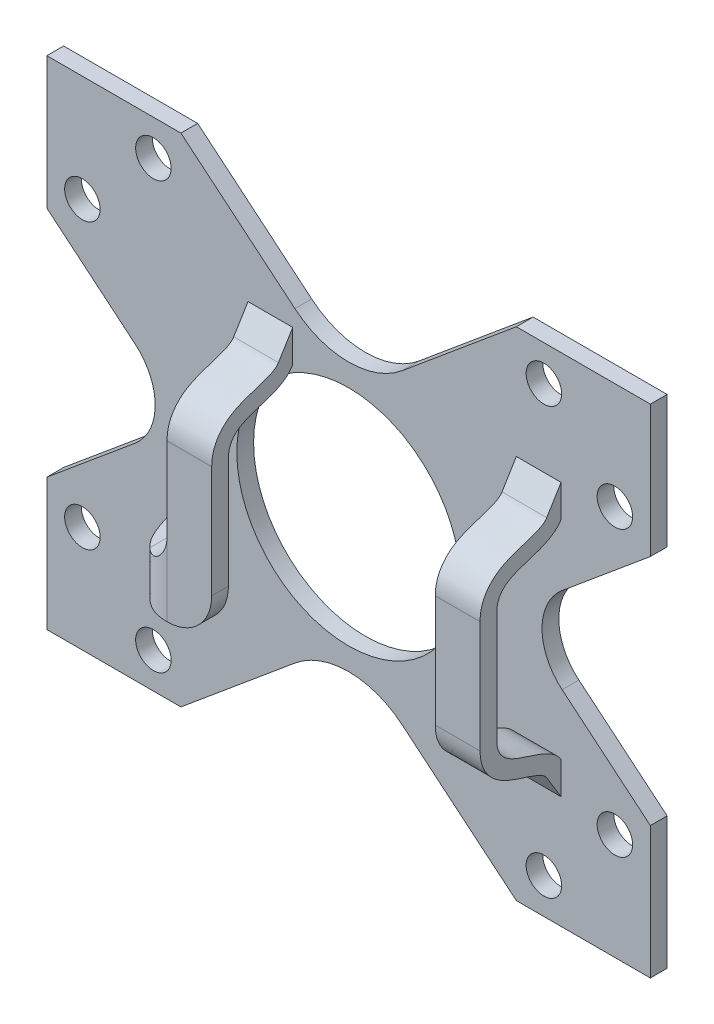
SolidWorks part; units mm, degrees
ref_plane "Front Plane" through (0, 0, 0) normal (0, 0, 1) x (1, 0, 0)
ref_plane "Top Plane" through (0, 0, 0) normal (0, 1, 0) x (1, 0, 0)
ref_plane "Right Plane" through (0, 0, 0) normal (1, 0, 0) x (0, 0, -1)
sketch "Sketch1" plane through (0, 0, 0) normal (0, 0, 1) x (1, 0, 0)
  line L1 (-53.975, -44.45) -> (53.975, -44.45)
  line L2 (-53.975, -44.45) -> (-53.975, 44.45)
  line L3 (-53.975, 44.45) -> (53.975, 44.45)
  line L4 (53.975, -44.45) -> (53.975, 44.45)
  line L5 (-53.975, -44.45) -> (53.975, 44.45) construction
  line L6 (-53.975, 44.45) -> (53.975, -44.45) construction
  line L12 (0, 44.45) -> (0, 19.45) construction
  line L13 (9.6028, 27.4523) -> (30, 44.45)
  line L14 (-9.6028, 27.4523) -> (-30, 44.45)
  line L15 (-9.6028, -27.4523) -> (-30, -44.45)
  line L16 (9.6028, -27.4523) -> (30, -44.45)
  line L17 (53.975, 0) -> (28.975, 0) construction
  line L18 (38.1937, 7.6822) -> (53.975, 20.8333)
  line L19 (38.1937, -7.6822) -> (53.975, -20.8333)
  line L20 (-38.1937, -7.6822) -> (-53.975, -20.8333)
  line L21 (-38.1937, 7.6822) -> (-53.975, 20.8333)
  circle A0 centre (34.925, 38.1) radius 3.175
  circle A1 centre (-34.925, 38.1) radius 3.175
  circle A2 centre (-47.625, 25.4) radius 3.175
  circle A3 centre (-47.625, -25.4) radius 3.175
  circle A4 centre (-34.925, -38.1) radius 3.175
  circle A5 centre (34.925, -38.1) radius 3.175
  circle A6 centre (47.625, -25.4) radius 3.175
  circle A7 centre (47.625, 25.4) radius 3.175
  circle A8 centre (0, 0) radius 20
  arc A9 (9.6028, -27.4523) -> (-9.6028, -27.4523) centre (0, -38.9756) ccw
  arc A10 (-9.6028, 27.4523) -> (9.6028, 27.4523) centre (0, 38.9756) ccw
  arc A11 (-38.1937, 7.6822) -> (-38.1937, -7.6822) centre (-44.5955, 0) cw
  arc A12 (38.1937, 7.6822) -> (38.1937, -7.6822) centre (44.5955, 0) ccw
  point P0 (0, 0)
  point P45 (0, 0)
  point P54 (0, 0)
  dimension "D3" = 40
  dimension "D8" = 15
  dimension "D9" = 10
  dimension "D4" = 25
  dimension "D5" = 30
  dimension "D7" = 2
  dimension "D6" = 2
extrude "Boss-Extrude1" add sketch "Sketch1" along normal blind 3 contours A12 L18 L4 L3 L13 A10 L14 L2 L21 A11 L20 L1 L15 A9 L16 L19 A8 A7 A6 A5 A4 A3 A2 A1 A0 region at (-52.5766, -32.6417, 0)
sketch "Sketch2" plane through (30, 0, 0) normal (1, 0, 0) x (0, 1, 0)
  line L0 (10, 44.6) -> (10, 14) construction
  line L1 (10, 14.5) -> (-10, 14.5)
  line L2 (10, 14.5) -> (10, 17.5)
  line L3 (10, 17.5) -> (-10, 17.5)
  line L4 (-10, 14.5) -> (-10, 17.5)
  line L5 (-10, 44.6) -> (-10, 14) construction
  line L6 (-27.4523, 3) -> (-44.45, 3) construction
  line L7 (0, 17.5) -> (0, 14.5) construction
  line L8 (18.5899, 3) -> (24.3467, 3)
  line L9 (20.1533, 5.5604) -> (24.3467, 3)
  line L10 (20.8333, 3) -> (44.45, 3) construction
  line L11 (-20.1533, 5.5604) -> (-24.3467, 3)
  line L12 (-18.5899, 3) -> (-24.3467, 3)
  line L13 (10, 14.5) -> (10, 17.5)
  line L16 (10.0308, 17.4998) -> (10, 17.5)
  line L17 (-10, 17.5) -> (-10.0308, 17.4998)
  spline S0 degree 3 poles (10, 14.5) (16.0446, 14.4379) (14.1847, 5.6897) (18.5899, 3) knots 0 0 0 0 1 1 1 1
  spline S1 degree 1 poles (10.0308, 17.4998) (20.1533, 5.5604) knots 0 0 1 1 construction
  spline S2 degree 3 poles (10.0308, 17.4998) (10.5803, 17.4942) (11.6908, 17.3812) (13.7449, 16.6992) (15.7401, 15.0501) (17.0126, 12.7979) (17.7868, 10.6515) (18.3801, 8.6858) (18.9697, 7.0604) (19.4886, 6.1722) (19.8692, 5.7606) (20.0511, 5.6229) (20.1533, 5.5604) knots 0 0 0 0 0.0625 0.125 0.25 0.375 0.5 0.625 0.75 0.875 0.9375 1 1 1 1
  spline S3 degree 3 poles (-10, 14.5) (-16.0446, 14.4379) (-14.1847, 5.6897) (-18.5899, 3) knots 0 0 0 0 1 1 1 1
  spline S4 degree 3 poles (-10.0308, 17.4998) (-10.5803, 17.4942) (-11.6908, 17.3812) (-13.7449, 16.6992) (-15.7401, 15.0501) (-17.0126, 12.7979) (-17.7868, 10.6515) (-18.3801, 8.6858) (-18.9697, 7.0604) (-19.4886, 6.1722) (-19.8692, 5.7606) (-20.0511, 5.6229) (-20.1533, 5.5604) knots 0 0 0 0 0.0625 0.125 0.25 0.375 0.5 0.625 0.75 0.875 0.9375 1 1 1 1
  line M4 (10, 14) -> (10, 44.6)
  line M6 (-10, 44.6) -> (-10, 14)
  dimension "D1" = 11.5
  dimension "D2" = 3
  dimension "D3" = 3
  dimension "D4" = 1.3736
extrude "Boss-Extrude2" add sketch "Sketch2" along normal blind 8 contours S2 L16 S0 L8 L9 M4 | L3 L1 M4 M6 | L17 S4 L11 L12 S3 M6 region at (30, 0, 16) region at (30, 16.1443, 10.0739) region at (30, -16.1443, 10.074)
sketch "Sketch3" plane through (-10, 0, 0) normal (-1, 0, 0) x (0, 0, 1)
  line L1 (3, 7.6822) -> (3, 20.8333) construction
  line L3 (44.6, -10) -> (14, -10) construction
  line L4 (14.5, 10) -> (14.5, -10) construction
  line L8 (44.6, 10) -> (14, 10) construction
  line L10 (14.5, -10) -> (14.5, 10)
  line L11 (14.5, -10) -> (17.5, -10)
  line L12 (17.5, -10) -> (17.5, 10)
  line L13 (14.5, 10) -> (17.5, 10)
  line L14 (17.5, 0) -> (14.5, 0) construction
  line L15 (5.5516, 20.1677) -> (3, 24.3467)
  line L16 (3, 18.6097) -> (3, 24.3467)
  line L17 (14.5, -10) -> (17.5, -10)
  line L18 (17.491, -10.0452) -> (17.5, -10)
  line L19 (17.5, 10) -> (17.491, 10.0452)
  line L20 (5.5604, 20.1533) -> (3, 24.3467) construction
  spline S2 degree 3 poles (14.5, 10) (14.3156, 16.0357) (5.4935, 14.0529) (3, 18.6097) knots 0 0 0 0 1 1 1 1
  spline S3 degree 3 poles (17.491, 10.0452) (17.4854, 10.5947) (17.3724, 11.7053) (16.6904, 13.7593) (15.0413, 15.7545) (12.7891, 17.0271) (10.6427, 17.8012) (8.677, 18.3945) (7.0516, 18.9842) (6.1634, 19.503) (5.7518, 19.8837) (5.614, 20.0655) (5.5516, 20.1677) knots 0 0 0 0 0.0625 0.125 0.25 0.375 0.5 0.625 0.75 0.875 0.9375 1 1 1 1
  line M9 (14, -10) -> (44.6, -10)
  line M11 (44.6, 10) -> (14, 10)
  dimension "D2" = 3
extrude "Boss-Extrude3" add sketch "Sketch3" along normal blind 8 contours L14 L12 L10 M11 | L12 L14 L10 M9 | L19 S3 L15 L16 S2 M11 region at (-10, -5, 16) region at (-10, 5, 16) region at (-10, 16.1276, 10.0554)
sketch "Sketch4" plane through (0, 0, 14.5) normal (0, 0, -1) x (-1, 0, 0)
  line L0 (18, -18) -> (18, -10)
  line L1 (10, -10) -> (18, -10)
  arc A0 (10, -10) -> (18, -18) centre (18, -10) ccw
extrude "Boss-Extrude4" add sketch "Sketch4" against normal up to surface (3 mm away) up to face at (-14, 0, 17.5)
sketch "Sketch5" plane through (0, -10, 0) normal (0, -1, 0) x (1, 0, 0)
  line L13 (-18, 14.5) -> (-18, 17.5)
  line L15 (-28.113, 5.5355) -> (-32.3195, 2.9671)
  line L16 (-26.5627, 2.9671) -> (-32.3195, 2.9671)
  line L19 (-18, 17.5) -> (-18.019, 17.499)
  spline S2 degree 3 poles (-18, 14.5) (-24.0013, 14.3313) (-22.1635, 5.6592) (-26.5627, 2.9671) knots 0 0 0 0 1 1 1 1
  spline S3 degree 3 poles (-18.019, 17.499) (-18.5684, 17.4921) (-19.6787, 17.3764) (-21.7311, 16.6895) (-23.7224, 15.0356) (-24.9896, 12.7805) (-25.7586, 10.6322) (-26.3472, 8.6651) (-26.933, 7.0383) (-27.4497, 6.1489) (-27.8294, 5.7364) (-28.0109, 5.5982) (-28.113, 5.5355) knots 0 0 0 0 0.0625 0.125 0.25 0.375 0.5 0.625 0.75 0.875 0.9375 1 1 1 1
  point P0 (-18.019, 17.499)
  point P13 (0, 0)
extrude "Boss-Extrude5" add sketch "Sketch5" along normal blind 8
fillet "Fillet1" radius 5 1 edges
